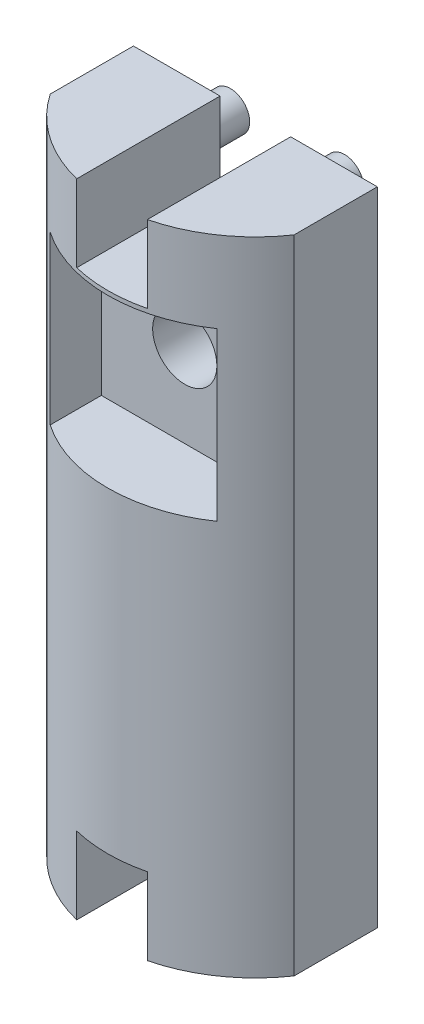
SolidWorks part; units mm, degrees
material "ABS"
ref_plane "Спереди" through (0, 0, 0) normal (0, 0, 1) x (1, 0, 0)
ref_plane "Сверху" through (0, 0, 0) normal (0, 1, 0) x (1, 0, 0)
ref_plane "Справа" through (0, 0, 0) normal (1, 0, 0) x (0, 0, -1)
sketch "Эскиз1" plane through (0, 0, 0) normal (0, 1, 0) x (1, 0, 0)
  line L0 (-23, 0) -> (23, 0)
  arc A0 (-23, 0) -> (23, 0) centre (0, 0) ccw
  dimension "D1" = 23
extrude "Бобышка-Вытянуть1" add sketch "Эскиз1" along normal blind 100
sketch "Эскиз2" plane through (0, 0, 0) normal (0, 0, -1) x (-1, 0, 0)
  line L0 (0, 100) -> (0, 0) construction
  line L1 (-23, 100) -> (23, 100) construction
  line L2 (-23, 50) -> (5.22, 50) construction
  line L3 (-23, 100) -> (-23, 0) construction
  line L4 (-8.89, 93.815) -> (8.89, 93.815) construction
  line L5 (-8.89, 93.815) -> (-8.89, 6.185) construction
  circle A0 centre (-8.89, 93.815) radius 3
  circle A1 centre (8.89, 93.815) radius 3
  circle A2 centre (-8.89, 6.185) radius 3
  circle A3 centre (8.89, 6.185) radius 3
  circle A4 centre (-8.89, 93.815) radius 0.9
  circle A5 centre (8.89, 93.815) radius 0.9
  circle A6 centre (8.89, 6.185) radius 0.9
  circle A7 centre (-8.89, 6.185) radius 0.9
  point P17 (0, 93.815)
  point P19 (-8.89, 50)
  dimension "D1" = 6
  dimension "D4" = 1.8
  dimension "D2" = 2
  dimension "D3" = 2
extrude "Бобышка-Вытянуть2" add sketch "Эскиз2" along normal blind 5
sketch "Эскиз4" plane through (0, 0, 0) normal (0, 0, -1) x (-1, 0, 0)
  line L0 (-23, 0) -> (23, 0) construction
  line L1 (-19, 0) -> (19, 0)
  line L2 (-19, 0) -> (-19, 100)
  line L3 (-19, 100) -> (19, 100)
  line L4 (19, 0) -> (19, 100)
  line L5 (-23, 100) -> (23, 100) construction
  line L7 (-33.2966, 110.6364) -> (33.2966, 110.6364)
  line L8 (-33.2966, 110.6364) -> (-33.2966, -11.5529)
  line L9 (-33.2966, -11.5529) -> (33.2966, -11.5529)
  line L10 (33.2966, 110.6364) -> (33.2966, -11.5529)
  line L11 (-33.2966, 110.6364) -> (33.2966, -11.5529) construction
  line L12 (-33.2966, -11.5529) -> (33.2966, 110.6364) construction
  point P8 (0, 0)
  point P10 (0, 49.5418)
  dimension "D1" = 38
extrude "Вырез-Вытянуть1" cut sketch "Эскиз4" against normal through all
sketch "Эскиз5" plane through (0, 0, 0) normal (0, 0, -1) x (-1, 0, 0)
  line L0 (0, 100) -> (0, 55.9109) construction
  line L1 (-19, 100) -> (19, 100) construction
  line L3 (-13, 87.3507) -> (13, 87.3507)
  line L4 (-13, 87.3507) -> (-13, 61.3507)
  line L5 (-13, 61.3507) -> (13, 61.3507)
  line L6 (13, 87.3507) -> (13, 61.3507)
  point P9 (0, 87.3507)
  dimension "D1" = 26
  dimension "D2" = 26
extrude "Вырез-Вытянуть2" cut sketch "Эскиз5" along normal blind 12 from offset 23 offset against normal yes
sketch "Эскиз6" plane through (0, 0, 11) normal (0, 0, 1) x (1, 0, 0)
  circle A0 centre (0, 74.3507) radius 5
extrude "Вырез-Вытянуть3" cut sketch "Эскиз6" against normal blind 32
sketch "Эскиз7" plane through (0, 0, 0) normal (0, 0, -1) x (-1, 0, 0)
  line L0 (0, 100) -> (0, 63.0188) construction
  line L1 (-19, 100) -> (19, 100) construction
  line L2 (-19, 50) -> (66.3132, 50) construction
  line L3 (-5.5, 100) -> (5.5, 100)
  line L4 (-5.5, 100) -> (-5.5, 88)
  line L5 (-5.5, 88) -> (5.5, 88)
  line L6 (5.5, 100) -> (5.5, 88)
  line L7 (-19, 100) -> (-19, 0) construction
  line L8 (5.5, 0) -> (5.5, 12)
  line L9 (-5.5, 12) -> (5.5, 12)
  line L10 (-5.5, 0) -> (-5.5, 12)
  line L11 (-5.5, 0) -> (5.5, 0)
  point P9 (0, 100)
  dimension "D1" = 11
  dimension "D2" = 12
extrude "Вырез-Вытянуть4" cut sketch "Эскиз7" against normal through all
sketch "Эскиз8" plane through (0, 0, 0) normal (0, 0, -1) x (-1, 0, 0)
  line L0 (-5.5, 88) -> (5.5, 88) construction
  line L1 (-10, 88) -> (10, 88)
  line L2 (-10, 88) -> (-10, 38)
  line L3 (-10, 38) -> (10, 38)
  line L4 (10, 88) -> (10, 38)
  point P4 (0, 88)
  point P7 (0, 88)
  dimension "D1" = 50
  dimension "D2" = 20
extrude "Вырез-Вытянуть5" cut sketch "Эскиз8" against normal blind 3
